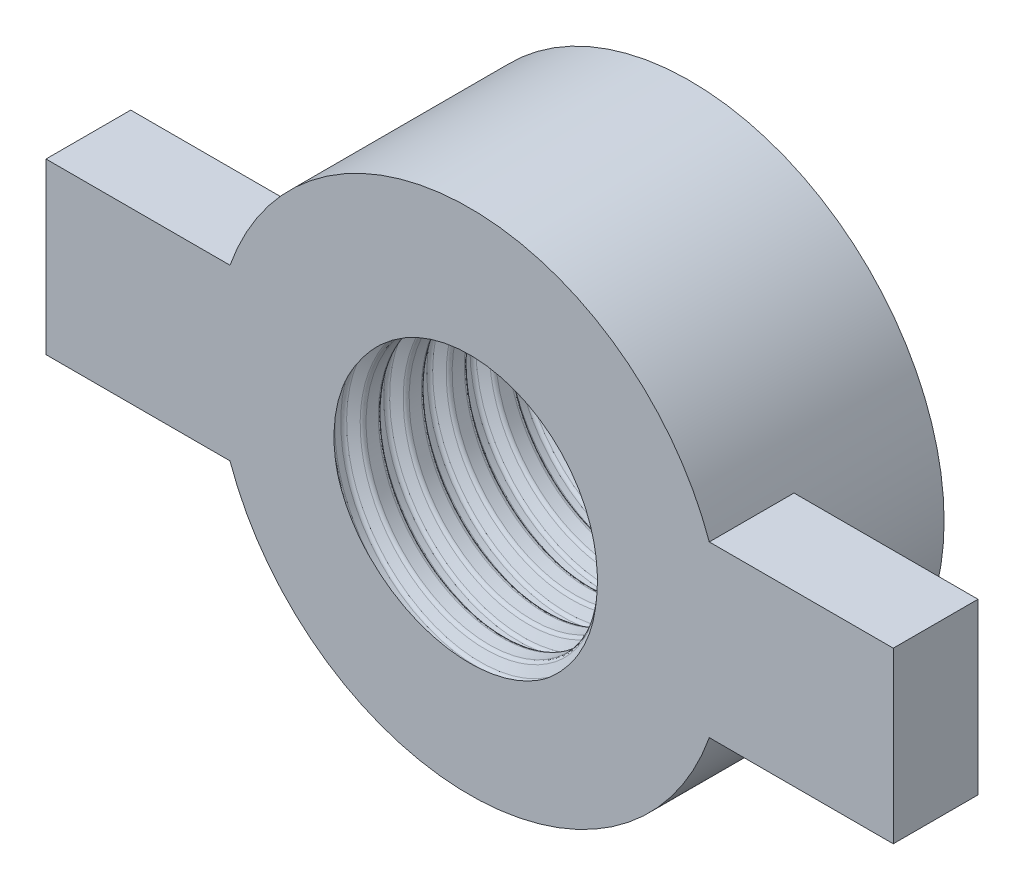
SolidWorks part; units mm, degrees
ref_plane "Front Plane" through (0, 0, 0) normal (0, 0, 1) x (1, 0, 0)
ref_plane "Top Plane" through (0, 0, 0) normal (0, 1, 0) x (1, 0, 0)
ref_plane "Right Plane" through (0, 0, 0) normal (1, 0, 0) x (0, 0, -1)
sketch "Sketch1" plane through (0, 0, 0) normal (0, 0, 1) x (1, 0, 0)
  circle A0 centre (0, 0) radius 30
  circle A1 centre (0, 0) radius 15
  dimension "D1" = 30
  dimension "D2" = 60
extrude "Boss-Extrude1" add sketch "Sketch1" along normal blind 26
thread "Thread1" pitch 5.08 method cut trim with start face yes profile "Thread Profile1" start angle 0, offset 11, length 40, pitch 5.08, diameter 30
ref_plane "Plane1" through (-15, 0, 37) normal (0, -1, 0) x (-1, 0, 0)
sketch "Thread Profile1" plane through (-15, 0, 37) normal (0, -1, 0) x (-1, 0, 0)
  line L0 (0, 0) -> (0, 5.08) construction
  line L1 (0, 0) -> (0, 3.6346)
  line L2 (0.508, 3.6346) -> (1.524, 3.6346) construction
  line L3 (1.524, 2.1681) -> (1.524, 1.4665)
  line L4 (1.27, 2.6081) -> (0.254, 3.1946)
  line L5 (1.27, 1.0265) -> (0.254, 0.4399)
  line L6 (0.508, 0) -> (1.524, 0) construction
  arc A0 (0.254, 3.1946) -> (0, 3.6346) centre (0.508, 3.6346) cw
  arc A1 (0.254, 0.4399) -> (0, 0) centre (0.508, 0) ccw
  arc A2 (1.524, 1.4665) -> (1.27, 1.0265) centre (1.016, 1.4665) cw
  arc A3 (1.524, 2.1681) -> (1.27, 2.6081) centre (1.016, 2.1681) ccw
  point P10 (1.524, 2.4614)
  point P17 (1.524, 1.1732)
  point P18 (0, 3.3413)
  point P19 (0, 0.2933)
  point P20 (0, 0)
  dimension "RootFillet1" = 0.508
  dimension "RootFillet2" = 0.508
  dimension "CrestFillet2" = 0.508
  dimension "CrestFillet1" = 0.508
  dimension "Pitch" = 5.08
  dimension "Angle1" = 30
  dimension "Angle2" = 30
  dimension "a" = 3.048
  dimension "b" = 1.524
  dimension "c" = 1.2882
sketch "Sketch2" plane through (0, 0, 26) normal (0, 0, 1) x (1, 0, 0)
  line L0 (0, -15.2478) -> (0, 15.2478) construction
  line L1 (-50, 10) -> (-20, 10)
  line L2 (-50, 10) -> (-50, -10)
  line L3 (-50, -10) -> (-20, -10)
  line L4 (-20, 10) -> (-20, -10)
  line L9 (20, 10) -> (20, -10)
  line L10 (50, -10) -> (20, -10)
  line L11 (50, 10) -> (50, -10)
  line L12 (50, 10) -> (20, 10)
  dimension "D1" = 20
  dimension "D2" = 30
  dimension "D3" = 10
  dimension "D4" = 20
extrude "Boss-Extrude2" add sketch "Sketch2" against normal blind 10
